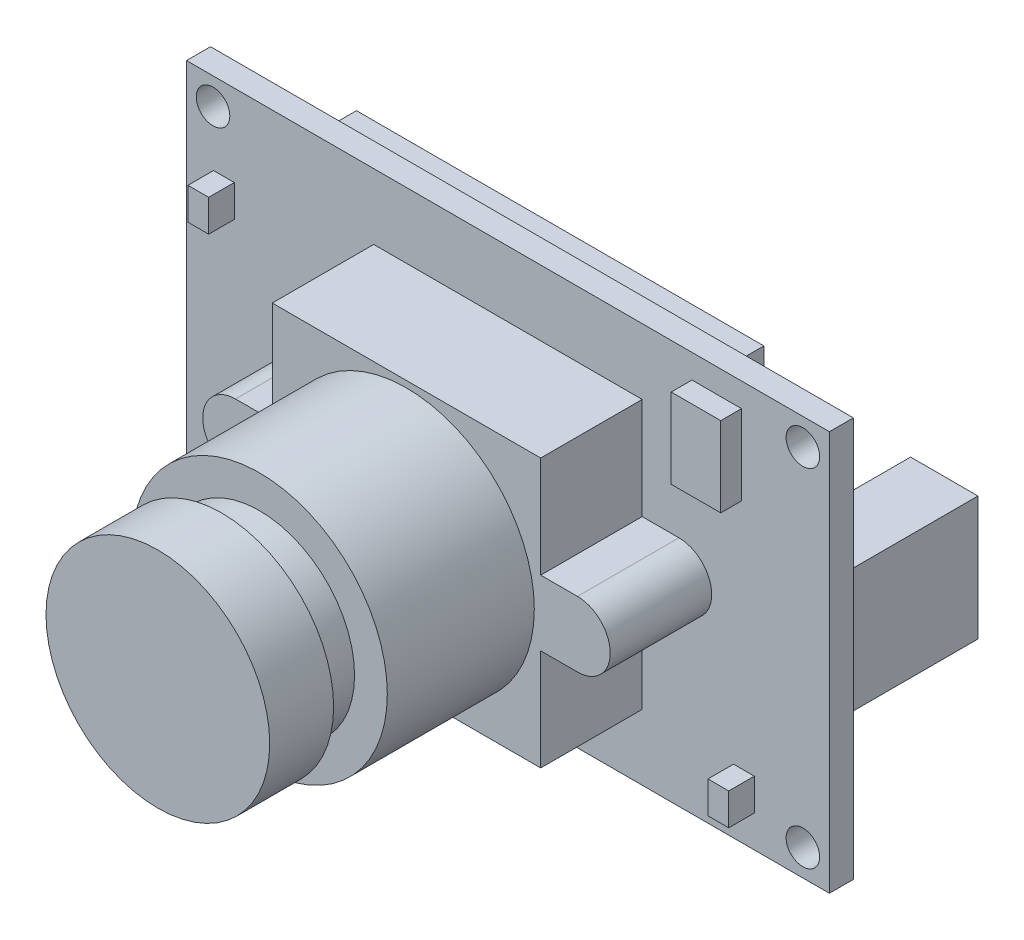
SolidWorks part; units mm, degrees
ref_plane "Front Plane" through (0, 0, 0) normal (0, 0, 1) x (1, 0, 0)
ref_plane "Top Plane" through (0, 0, 0) normal (0, 1, 0) x (1, 0, 0)
ref_plane "Right Plane" through (0, 0, 0) normal (1, 0, 0) x (0, 0, -1)
sketch "Sketch2" plane through (0, 0, 0) normal (0, 0, 1) x (1, 0, 0)
  line L0 (0, 0) -> (0, 6.003) construction
  line L1 (20.1168, 12.5095) -> (-20.1168, 12.5095)
  line L2 (20.1168, 12.5095) -> (20.1168, -12.5095)
  line L3 (20.1168, -12.5095) -> (-20.1168, -12.5095)
  line L4 (-20.1168, 12.5095) -> (-20.1168, -12.5095)
  line L5 (20.1168, 12.5095) -> (-20.1168, -12.5095) construction
  line L6 (20.1168, -12.5095) -> (-20.1168, 12.5095) construction
  line L7 (-1000, 0) -> (49000, 0) construction
  circle A0 centre (-18.4568, 10.8495) radius 1.05
  circle A1 centre (-18.4568, -10.8495) radius 1.05
  circle A2 centre (18.4568, -10.8495) radius 1.05
  circle A3 centre (18.4568, 10.8495) radius 1.05
  point P0 (0, 0)
  dimension "D5" = 2.1
  dimension "D1" = 40.2336
  dimension "D2" = 25.019
  dimension "D3" = 1.66
  dimension "D4" = 1.66
extrude "Boss-Extrude1" add sketch "Sketch2" along normal blind 1.5
sketch "Sketch3" plane through (0, 0, 1.5) normal (0, 0, 1) x (1, 0, 0)
  line L0 (-8.4, -2.05) -> (-8.4, -8.4)
  line L1 (8.4, 8.4) -> (-8.4, 8.4)
  line L2 (8.4, 8.4) -> (8.4, 2.05)
  line L3 (8.4, -8.4) -> (-8.4, -8.4)
  line L4 (-8.4, 8.4) -> (-8.4, 2.05)
  line L5 (8.4, 8.4) -> (-8.4, -8.4) construction
  line L6 (8.4, -8.4) -> (-8.4, 8.4) construction
  line L7 (-10.7, 2.05) -> (-8.4, 2.05)
  line L8 (0, -1000) -> (0, 49000) construction
  line L9 (-10.7, -2.05) -> (-8.4, -2.05)
  line L10 (10.7, 2.05) -> (8.4, 2.05)
  line L11 (10.7, -2.05) -> (8.4, -2.05)
  line L12 (8.4, -2.05) -> (8.4, -8.4)
  line L13 (-1000, 0) -> (49000, 0) construction
  arc A0 (-10.7, 2.05) -> (-10.7, -2.05) centre (-10.7, 0) ccw
  arc A1 (10.7, 2.05) -> (10.7, -2.05) centre (10.7, 0) cw
  point P0 (0, 0)
  dimension "D1" = 16.8
  dimension "D2" = 16.8
  dimension "D3" = 4.1
  dimension "D4" = 2.3
extrude "Boss-Extrude2" add sketch "Sketch3" along normal blind 6.35
sketch "Sketch4" plane through (0, 0, 7.85) normal (0, 0, 1) x (1, 0, 0)
  circle A0 centre (0, 0) radius 8
  dimension "D1" = 16
extrude "Boss-Extrude3" add sketch "Sketch4" along normal blind 9.2
sketch "Sketch5" plane through (0, 0, 17.05) normal (0, 0, 1) x (1, 0, 0)
  circle A0 centre (0, 0) radius 5.95
  dimension "D1" = 11.9
extrude "Boss-Extrude4" add sketch "Sketch5" along normal blind 2.36
sketch "Sketch6" plane through (0, 0, 19.41) normal (0, 0, 1) x (1, 0, 0)
  circle A0 centre (0, 0) radius 7
extrude "Boss-Extrude5" add sketch "Sketch6" along normal blind 4
sketch "Sketch7" plane through (0, 0, 0) normal (0, 0, -1) x (-1, 0, 0)
  line L0 (0, 0) -> (-20.1168, 0) construction
  line L1 (-15.3968, -3.875) -> (-19.6168, -3.875)
  line L2 (-15.3968, -3.875) -> (-15.3968, 3.875)
  line L3 (-15.3968, 3.875) -> (-19.6168, 3.875)
  line L4 (-19.6168, -3.875) -> (-19.6168, 3.875)
  line L5 (-20.1168, -12.5095) -> (-20.1168, 12.5095) construction
  point P9 (-19.6168, 0)
  dimension "D1" = 7.75
  dimension "D2" = 4.22
  dimension "D3" = 0.5
extrude "Boss-Extrude6" add sketch "Sketch7" along normal blind 8.3
sketch "Sketch8" plane through (0, 0, 0) normal (0, 0, -1) x (-1, 0, 0)
  line L0 (20.1168, 12.5095) -> (20.1168, -12.5095) construction
  line L1 (15.6768, -10.8695) -> (6.6768, -10.8695)
  line L2 (15.6768, -10.8695) -> (15.6768, -7.9395)
  line L3 (15.6768, -7.9395) -> (6.6768, -7.9395)
  line L4 (6.6768, -10.8695) -> (6.6768, -7.9395)
  line L5 (20.1168, -12.5095) -> (-20.1168, -12.5095) construction
  dimension "D1" = 4.44
  dimension "D2" = 1.64
  dimension "D3" = 9
  dimension "D4" = 2.93
extrude "Boss-Extrude7" add sketch "Sketch8" along normal blind 4.35
sketch "Sketch9" plane through (0, 0, 1.5) normal (0, 0, 1) x (1, 0, 0)
  line L0 (20.1168, -12.5095) -> (20.1168, 12.5095) construction
  line L1 (11.5168, 11.0095) -> (14.6168, 11.0095)
  line L2 (11.5168, 11.0095) -> (11.5168, 6.0095)
  line L3 (11.5168, 6.0095) -> (14.6168, 6.0095)
  line L4 (14.6168, 11.0095) -> (14.6168, 6.0095)
  line L5 (20.1168, 12.5095) -> (-20.1168, 12.5095) construction
  dimension "D1" = 3.1
  dimension "D2" = 5
  dimension "D3" = 5.5
  dimension "D4" = 1.5
extrude "Boss-Extrude8" add sketch "Sketch9" along normal blind 1.3
sketch "Sketch10" plane through (0, 0, 0) normal (0, 0, -1) x (-1, 0, 0)
  line L0 (-20.1168, -12.5095) -> (-20.1168, 12.5095) construction
  line L1 (-13.1168, 12.2095) -> (12.3832, 12.2095)
  line L2 (-13.1168, 12.2095) -> (-13.1168, 4.2095)
  line L3 (-13.1168, 4.2095) -> (12.3832, 4.2095)
  line L4 (12.3832, 12.2095) -> (12.3832, 4.2095)
  line L5 (-13.1168, 12.2095) -> (12.3832, 4.2095) construction
  line L6 (-13.1168, 4.2095) -> (12.3832, 12.2095) construction
  line L7 (-20.1168, 12.5095) -> (20.1168, 12.5095) construction
  point P0 (-0.3668, 8.2095)
  dimension "D1" = 25.5
  dimension "D2" = 8
  dimension "D3" = 7
  dimension "D4" = 0.3
extrude "Boss-Extrude9" add sketch "Sketch10" along normal blind 1.4
sketch "Sketch11" plane through (0, 0, 1.5) normal (0, 0, 1) x (1, 0, 0)
  line L0 (20.1168, -12.5095) -> (20.1168, 12.5095) construction
  line L1 (15.4168, -10.5095) -> (14.1168, -10.5095)
  line L2 (15.4168, -10.5095) -> (15.4168, -8.5095)
  line L3 (15.4168, -8.5095) -> (14.1168, -8.5095)
  line L4 (14.1168, -10.5095) -> (14.1168, -8.5095)
  line L5 (-20.1168, -12.5095) -> (20.1168, -12.5095) construction
  line L6 (-17.1271, 5.3916) -> (-18.4271, 5.3916)
  line L7 (-17.1271, 5.3916) -> (-17.1271, 7.3916)
  line L8 (-17.1271, 7.3916) -> (-18.4271, 7.3916)
  line L9 (-18.4271, 5.3916) -> (-18.4271, 7.3916)
  dimension "D1" = 1.3
  dimension "D2" = 2
  dimension "D3" = 6
  dimension "D4" = 2
extrude "Boss-Extrude10" add sketch "Sketch11" along normal blind 1.6
sketch "Sketch12" plane through (0, 0, 0) normal (0, 0, -1) x (-1, 0, 0)
  line L0 (-20.1168, 12.5095) -> (20.1168, 12.5095) construction
  line L1 (19.1168, 5.1095) -> (16.1168, 5.1095)
  line L2 (19.1168, 5.1095) -> (19.1168, 8.1095)
  line L3 (19.1168, 8.1095) -> (16.1168, 8.1095)
  line L4 (16.1168, 5.1095) -> (16.1168, 8.1095)
  line L5 (20.1168, 12.5095) -> (20.1168, -12.5095) construction
  dimension "D1" = 3
  dimension "D2" = 3
  dimension "D3" = 7.4
  dimension "D4" = 1
extrude "Boss-Extrude11" add sketch "Sketch12" along normal blind 1.4
sketch "Sketch13" plane through (0, 0, 0) normal (0, 0, -1) x (-1, 0, 0)
  line L0 (-20.1168, -12.5095) -> (-20.1168, 12.5095) construction
  line L1 (-14.1478, -9.3853) -> (-10.9728, -9.3853)
  line L2 (-14.1478, -9.3853) -> (-14.1478, -12.0015)
  line L3 (-14.1478, -12.0015) -> (-10.9728, -12.0015)
  line L4 (-10.9728, -9.3853) -> (-10.9728, -12.0015)
  line L5 (20.1168, -12.5095) -> (-20.1168, -12.5095) construction
  line L7 (-7.1628, -7.1755) -> (1.3462, -7.1755)
  line L8 (-7.1628, -7.1755) -> (-7.1628, -12.0015)
  line L9 (-7.1628, -12.0015) -> (1.3462, -12.0015)
  line L10 (1.3462, -7.1755) -> (1.3462, -12.0015)
  dimension "D1" = 3.175
  dimension "D2" = 2.6162
  dimension "D3" = 5.969
  dimension "D4" = 0.508
  dimension "D5" = 8.509
  dimension "D6" = 4.826
  dimension "D7" = 12.954
  dimension "D8" = 0.508
extrude "Boss-Extrude12" add sketch "Sketch13" along normal blind 2.7432
move or copy body "Body-Move/Copy1" [suppressed] bodies to move or copy 112
